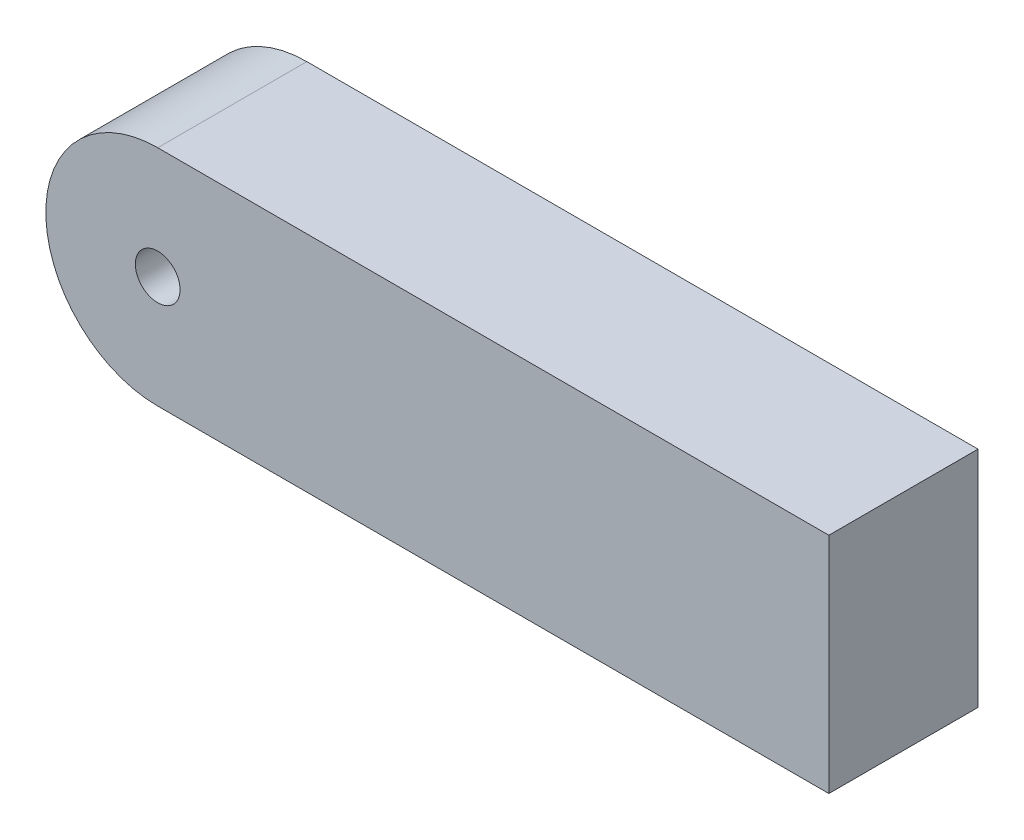
SolidWorks part; units mm, degrees
ref_plane "前视基准面" through (0, 0, 0) normal (0, 0, 1) x (1, 0, 0)
ref_plane "上视基准面" through (0, 0, 0) normal (0, 1, 0) x (1, 0, 0)
ref_plane "右视基准面" through (0, 0, 0) normal (1, 0, 0) x (0, 0, -1)
sketch "草图1" plane through (0, 0, 0) normal (0, 0, 1) x (1, 0, 0)
  line L1 (-45, 15) -> (45, 15)
  line L3 (-45, -15) -> (45, -15)
  line L4 (45, 15) -> (45, -15)
  arc A0 (-45, 15) -> (-45, -15) centre (-45, 0) ccw
  circle A1 centre (-45, 0) radius 3
  point P0 (0, 0)
  dimension "D1" = 30
extrude "凸台-拉伸1" add sketch "草图1" along normal blind 20
